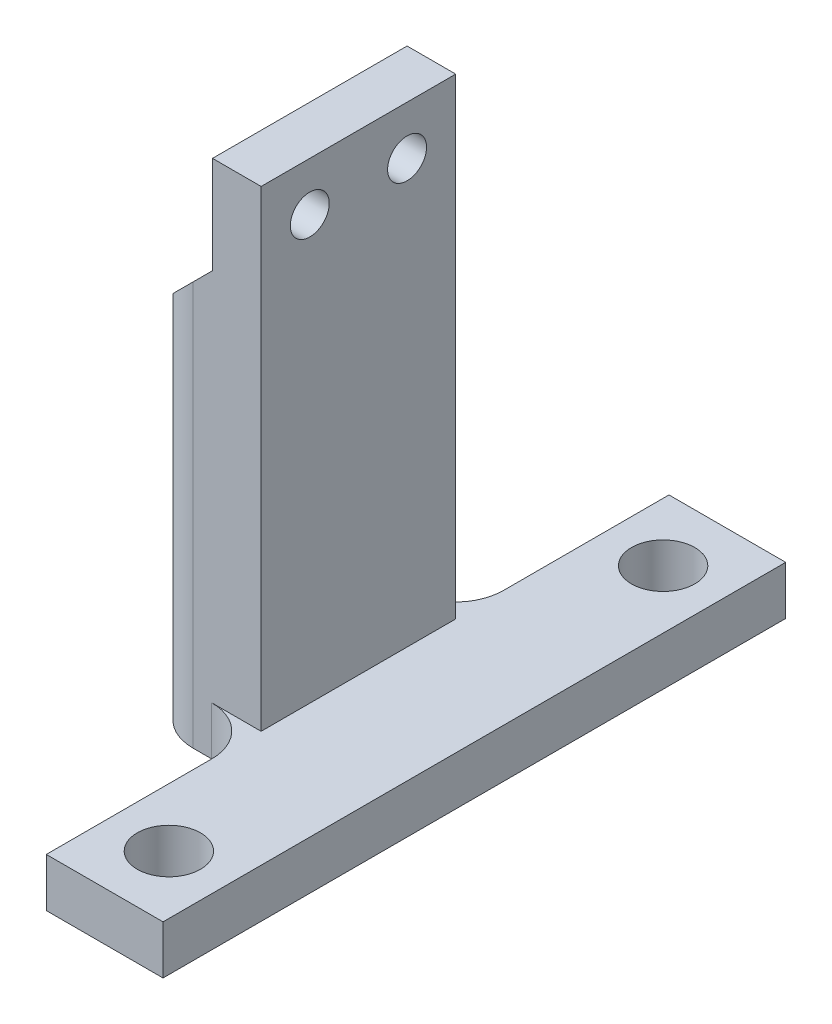
SolidWorks part; units mm, degrees
ref_plane "Front Plane" through (0, 0, 0) normal (0, 0, 1) x (1, 0, 0)
ref_plane "Top Plane" through (0, 0, 0) normal (0, 1, 0) x (1, 0, 0)
ref_plane "Right Plane" through (0, 0, 0) normal (1, 0, 0) x (0, 0, -1)
sketch "Sketch1" plane through (0, 0, 0) normal (0, 1, 0) x (1, 0, 0)
  line L8 (0, -10) -> (0, 10)
  line L14 (11.9172, 32) -> (11.9172, 10)
  line L15 (11.9172, 10) -> (0, 10)
  line L18 (23.9172, 32) -> (23.9172, -32)
  line L20 (11.9172, -10) -> (11.9172, -32)
  line L22 (11.9172, -10) -> (0, -10)
  line L23 (11.9172, -32) -> (23.9172, -32)
  line L24 (11.9172, 32) -> (23.9172, 32)
  point P13 (0, 0)
  point P15 (12, 0)
  dimension "D2" = 64
  dimension "D3" = 20
  dimension "D4" = 32
  dimension "D11" = 12
  dimension "D12" = 0
  dimension "D15" = 12
extrude "Boss-Extrude1" add sketch "Sketch1" along normal blind 5
hole_wizard "1/4 (0.25) Clearance Dowel Hole2" positions "Sketch2" profile "Sketch3" hole size "1/4" standard "ANSI Inch" end condition through all
sketch "Sketch2" plane through (0, 5, 0) normal (0, 1, 0) x (1, 0, 0)
  line L8 (17.9172, -32) -> (17.9172, 32) construction
  line L9 (11.9172, -32) -> (23.9172, -32) construction
  line L10 (23.9172, 32) -> (11.9172, 32) construction
  point P0 (17.9172, -25.4)
  point P2 (17.9172, 25.4)
  dimension "D1" = 0
  dimension "D2" = 0
  dimension "D3" = 50.8
  dimension "D4" = 6.6
sketch "Sketch3" plane through (17.9172, 5, 25.4) normal (1, 0, 0) x (0, 0, 1)
  line L0 (0, 0) -> (0, 5)
  line L1 (0, 5) -> (3.25, 5)
  line L2 (3.25, 5) -> (3.25, 0)
  line L5 (3.25, 0) -> (0, 0)
  line L11 (0, -6.35) -> (0, 107.95) construction
  dimension "Thru Hole Dia." = 6.5
  dimension "Thru Hole Depth" = 5
sketch "Sketch4" plane through (0, 5, 0) normal (0, 1, 0) x (1, 0, 0)
  line L0 (0, 10) -> (0, -10)
  line L2 (0, -10) -> (12, -10)
  line L4 (12, -10) -> (12, 10)
  line L5 (12, 10) -> (0, 10)
  point P6 (0, 0)
  dimension "D1" = 20
sketch "Sketch8" plane through (0, 5, 0) normal (0, 1, 0) x (1, 0, 0)
  line L0 (0, 10) -> (0, -10) construction
  line L1 (11.9172, -10) -> (0, -10)
  line L2 (11.9172, -10) -> (11.9172, 10)
  line L3 (11.9172, 10) -> (0, 10)
  line L4 (0, -10) -> (0, 10)
  line L6 (11.9172, -10) -> (11.9172, -32) construction
  line L7 (11.9172, 10) -> (0, 10) construction
  line L8 (0, -10) -> (11.9172, -10) construction
  dimension "D1" = 0
  dimension "D2" = 0
  dimension "D3" = 0
extrude "Boss-Extrude2" add sketch "Sketch4" along normal blind 48.5
sketch "Sketch5" plane through (0, 0, 0) normal (-1, 0, 0) x (0, 0, 1)
  line L0 (-10, 53.5) -> (-10, 0) construction
  line L1 (-10, 43.5) -> (10, 43.5)
  line L2 (-10, 43.5) -> (-10, 53.5)
  line L3 (-10, 53.5) -> (10, 53.5)
  line L4 (10, 43.5) -> (10, 53.5)
  line L5 (-10, 53.5) -> (10, 53.5) construction
  dimension "D1" = 10
  dimension "D2" = 0
extrude "Cut-Extrude1" cut sketch "Sketch5" against normal blind 7
hole_wizard "Ø4.0mm Clearance Dowel Hole1" positions "Sketch6" profile "Sketch7" hole size "Ø4.0" standard "ANSI Metric" end condition through all
sketch "Sketch6" plane through (7, 0, 0) normal (-1, 0, 0) x (0, 0, 1)
  line L0 (-10, 43.5) -> (10, 43.5) construction
  line L1 (-10, 53.5) -> (-10, 43.5) construction
  line L2 (10, 43.5) -> (10, 53.5) construction
  point P0 (-5, 48.5)
  point P2 (5, 48.5)
  dimension "D1" = 5
  dimension "D2" = 0
  dimension "D3" = 5
  dimension "D4" = 5
sketch "Sketch7" plane through (7, 48.5, -5) normal (0, 1, 0) x (0, 0, 1)
  line L0 (0, 0) -> (0, 16.9172)
  line L1 (0, 16.9172) -> (2, 16.9172)
  line L2 (2, 16.9172) -> (2, 0)
  line L5 (2, 0) -> (0, 0)
  line L11 (0, -6.35) -> (0, 107.95) construction
  dimension "Thru Hole Dia." = 4
  dimension "Thru Hole Depth" = 16.9172
chamfer "Chamfer1" distance 7 angle 45 1 edges at (0, 43.5, 0)
fillet "Fillet1" radius 5 4 edges at (0, 18.25, 10) (0, 18.25, -10) (11.9172, 2.5, -10) (11.9172, 2.5, 10)
